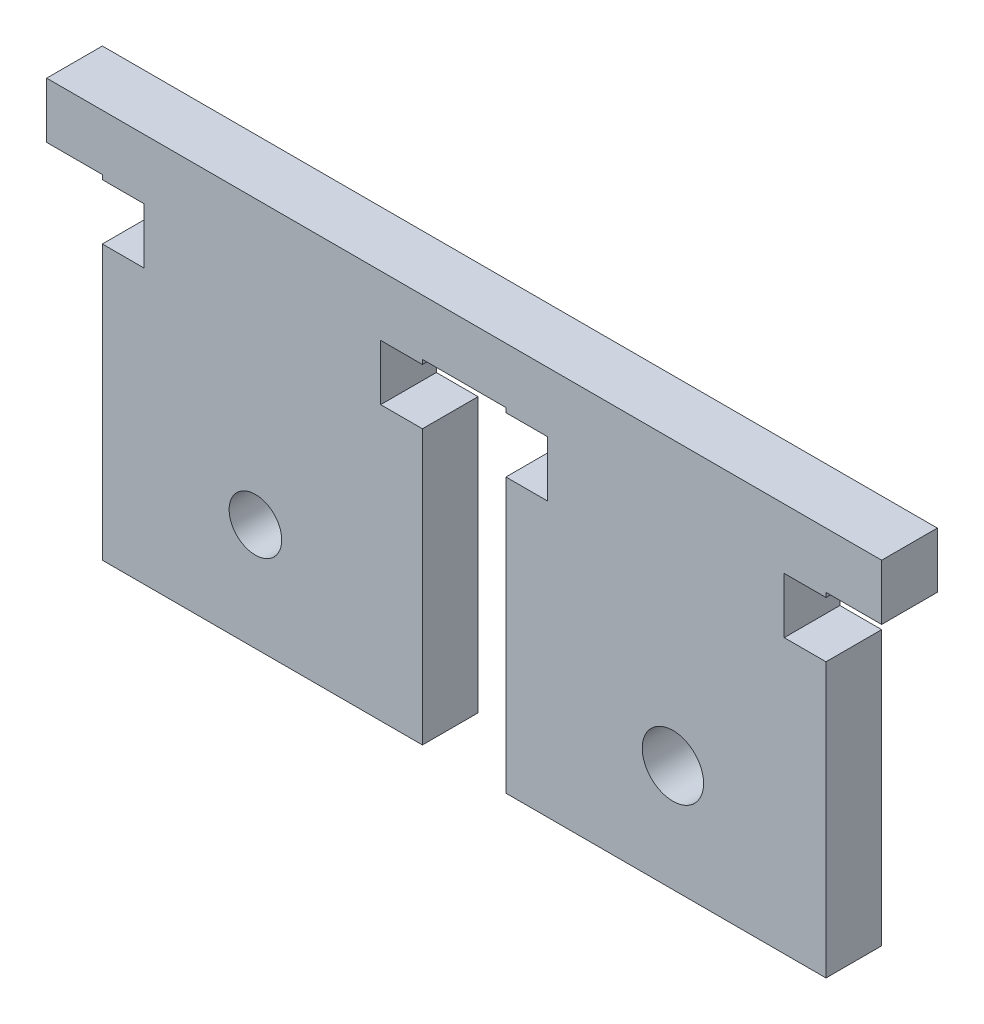
SolidWorks part; units mm, degrees
material "AISI 4130 Steel, annealed at 865C"
ref_plane "X-Y Datum" through (0, 0, 0) normal (0, 0, 1) x (1, 0, 0)
ref_plane "X-Z Datum" through (0, 0, 0) normal (0, 1, 0) x (1, 0, 0)
ref_plane "Y-Z Datum" through (0, 0, 0) normal (1, 0, 0) x (0, 0, -1)
sketch "Sketch3" plane through (0, 0, 0) normal (0, 0, 1) x (1, 0, 0)
  line L1 (-47.625, -30.48) -> (47.625, -30.48)
  line L2 (-47.625, -30.48) -> (-47.625, 30.48)
  line L3 (-47.625, 30.48) -> (47.625, 30.48)
  line L4 (47.625, -30.48) -> (47.625, 30.48)
  line L5 (-47.625, -30.48) -> (47.625, 30.48) construction
  line L6 (-47.625, 30.48) -> (47.625, -30.48) construction
  point P0 (0, 0)
  dimension "D1" = 95.25
  dimension "D2" = 60.96
extrude "Boss-Extrude1" add sketch "Sketch3" along normal blind 6.35
sketch "Sketch4" plane through (0, 0, 6.35) normal (0, 0, 1) x (1, 0, 0)
  line L0 (-47.625, 15.24) -> (-41.275, 15.24)
  line L1 (-47.625, 30.48) -> (-47.625, -30.48) construction
  line L2 (-41.275, 15.24) -> (-4.7625, 15.24)
  line L3 (-4.7625, 15.24) -> (4.7625, 15.24)
  line L4 (4.7625, 15.24) -> (41.275, 15.24)
  line L5 (41.275, 15.24) -> (47.625, 15.24)
  line L6 (47.625, -30.48) -> (47.625, 30.48) construction
  line L7 (0, 15.24) -> (0, -30.48) construction
  line L8 (-41.275, 15.24) -> (-47.625, 15.24)
  line L9 (-41.275, 15.24) -> (-41.275, -30.48)
  line L10 (-41.275, -30.48) -> (-47.625, -30.48)
  line L11 (-47.625, 15.24) -> (-47.625, -30.48)
  line L12 (-47.625, -30.48) -> (47.625, -30.48) construction
  line L13 (-1.5875, -16.0071) -> (1.5875, -16.0071)
  line L14 (-1.5875, -16.0071) -> (-1.5875, 0.7671)
  line L17 (-4.7625, 15.24) -> (4.7625, 15.24)
  line L19 (-4.7625, -30.48) -> (4.7625, -30.48)
  line L20 (-4.7625, -30.48) -> (-4.7625, 15.24)
  line L25 (-4.7625, 15.24) -> (4.7625, 15.24)
  line L26 (4.7625, -30.48) -> (4.7625, 15.24)
  line L27 (41.275, 15.24) -> (47.625, 15.24)
  line L28 (41.275, 15.24) -> (41.275, -30.48)
  line L29 (41.275, -30.48) -> (47.625, -30.48)
  line L31 (-4.7625, -30.48) -> (4.7625, 15.24) construction
  line L32 (-4.7625, 15.24) -> (4.7625, -30.48) construction
  line L33 (-1.5875, 0.7671) -> (1.5875, 0.7671)
  line L34 (1.5875, -16.0071) -> (1.5875, 0.7671)
  line L35 (-1.5875, -16.0071) -> (1.5875, 0.7671) construction
  line L36 (-1.5875, 0.7671) -> (1.5875, -16.0071) construction
  point P15 (0, -7.62)
  point P20 (0, -7.62)
  line M5 (47.625, -30.48) -> (47.625, 30.48)
  line M7 (-47.625, 30.48) -> (-47.625, -30.48)
  line M8 (-47.625, -30.48) -> (47.625, -30.48)
  dimension "D1" = 6.35
  dimension "D2" = 36.5125
  dimension "D3" = 6.35
  dimension "D4" = 36.5125
  dimension "D5" = 9.525
  dimension "D6" = 45.72
  dimension "D7" = 3.175
  dimension "D8" = 42.8625
  dimension "D9" = 45.72
extrude "Cut-Extrude1" cut sketch "Sketch4" against normal blind 6.35 contours L9 L0 M7 M8 | L3 M8 | L5 L28 M8 M5 | L13 L34 L33 L14 region at (-44.45, -7.62, 6.35) region at (0, 14.773, 6.35) region at (44.45, -7.62, 6.35) region at (0, -7.62, 6.35)
sketch "Sketch5" plane through (0, 0, 6.35) normal (0, 0, 1) x (1, 0, 0)
  line L9 (-23.0188, -30.48) -> (-23.0188, 30.48) construction
  line L10 (-41.275, 8.382) -> (-36.5125, 8.382)
  line L11 (-41.275, 8.382) -> (-41.275, 14.732)
  line L12 (-41.275, 14.732) -> (-36.5125, 14.732)
  line L13 (-36.5125, 8.382) -> (-36.5125, 14.732)
  line L14 (-41.275, -30.48) -> (-4.7625, -30.48) construction
  line L15 (47.625, 30.48) -> (-47.625, 30.48) construction
  line L16 (-41.275, 14.732) -> (-47.6562, 14.732)
  line L17 (-4.7625, 8.382) -> (-9.525, 8.382)
  line L18 (-4.7625, 8.382) -> (-4.7625, 14.732)
  line L19 (-4.7625, 14.732) -> (-9.525, 14.732)
  line L20 (-9.525, 8.382) -> (-9.525, 14.732)
  line L21 (-41.275, 14.732) -> (-41.275, 8.382)
  line L22 (-41.275, 8.382) -> (-47.6562, 8.382)
  line L23 (-47.6562, 14.732) -> (-47.6562, 8.382)
  line M5 (-41.275, 15.24) -> (-41.275, -30.48)
  line M15 (-47.625, 30.48) -> (-47.625, 15.24)
  line M16 (-47.625, 15.24) -> (-41.275, 15.24)
  dimension "D1" = 6.35
  dimension "D2" = 4.7625
  dimension "D3" = 15.748
extrude "Cut-Extrude2" cut sketch "Sketch5" against normal blind 6.35 contours L10 L13 L12 L11 | L20 L17 L18 L19 | L16 L23 L22 M5 M16 M15 region at (-38.8938, 11.557, 6.35) region at (-44.4656, 11.557, 6.35) region at (-7.1437, 11.557, 6.35)
mirror "Mirror1" about plane through (0, 0, 0) normal (1, 0, 0) of "Cut-Extrude2"
sketch "Sketch8" [suppressed] plane through (0, 15.24, 0) normal (0, -1, 0) x (1, 0, 0)
  line L0 (-9.525, 3.175) -> (9.525, 3.175) construction
  line L1 (-9.525, 0) -> (-9.525, 6.35) construction
  line L2 (9.525, 0) -> (9.525, 6.35) construction
  line L3 (-4.7625, 6.35) -> (4.7625, 6.35) construction
  line L4 (-4.7625, 0) -> (4.7625, 0)
  line L5 (-4.7625, 0) -> (-4.7625, 6.35)
  line L6 (-4.7625, 6.35) -> (4.7625, 6.35)
  line L7 (4.7625, 0) -> (4.7625, 6.35)
  line L8 (-4.7625, 0) -> (4.7625, 6.35) construction
  line L9 (-4.7625, 6.35) -> (4.7625, 0) construction
  point P6 (0, 3.175)
  line M3 (-4.7625, 0) -> (4.7625, 0)
  dimension "D1" = 4.7625
extrude "Cut-Extrude3" [suppressed] cut sketch "Sketch8" against normal blind 1.5875 contours L7 L0 L5 M3
sketch "Sketch9" plane through (0, 30.48, 0) normal (0, 1, 0) x (1, 0, 0)
  line L1 (-47.625, 0) -> (47.625, 0)
  line L2 (-47.625, 0) -> (-47.625, -6.35)
  line L3 (-47.625, -6.35) -> (47.625, -6.35)
  line L4 (47.625, 0) -> (47.625, -6.35)
extrude "Cut-Extrude6" cut sketch "Sketch9" against normal blind 8.89
sketch "Sketch10" plane through (0, 0, 6.35) normal (0, 0, 1) x (1, 0, 0)
  circle A0 centre (-23.8125, -10.6279) radius 3 construction
  circle A2 centre (-23.8125, -10.6279) radius 3
  circle A3 centre (23.8138, -10.6279) radius 3.5
extrude "Cut-Extrude7" cut sketch "Sketch10" against normal blind 6.35
sketch "Sketch11" plane through (0, -30.48, 0) normal (0, -1, 0) x (1, 0, 0)
  line L1 (-41.275, 6.35) -> (41.275, 6.35)
  line L2 (-41.275, 6.35) -> (-41.275, 0)
  line L3 (-41.275, 0) -> (41.275, 0)
  line L4 (41.275, 6.35) -> (41.275, 0)
extrude "Cut-Extrude9" cut sketch "Sketch11" against normal blind 7.62
